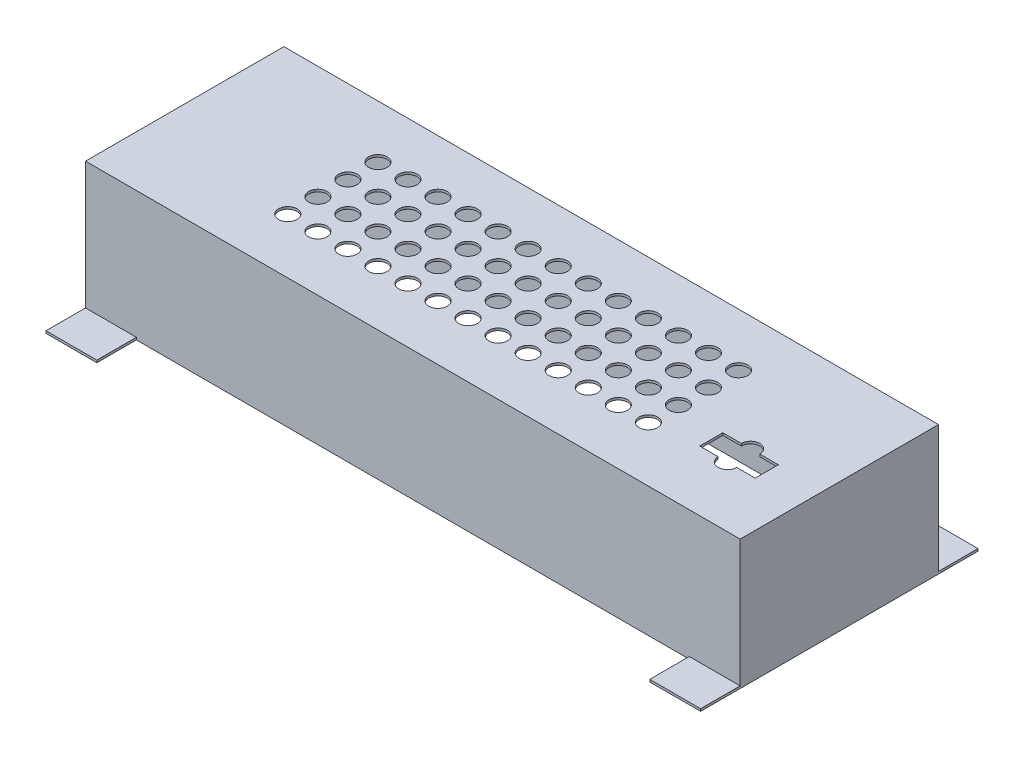
SolidWorks part; units mm, degrees
material "Lega 1060"
ref_plane "Piano frontale" through (0, 0, 0) normal (0, 0, 1) x (1, 0, 0)
ref_plane "Piano superiore" through (0, 0, 0) normal (0, 1, 0) x (1, 0, 0)
ref_plane "Piano destro" through (0, 0, 0) normal (1, 0, 0) x (0, 0, -1)
sketch "Schizzo1" plane through (0, 0, 0) normal (0, 1, 0) x (1, 0, 0)
  line L1 (-70.8, -21.45) -> (70.8, -21.45)
  line L2 (-70.8, -21.45) -> (-70.8, 21.45)
  line L3 (-70.8, 21.45) -> (70.8, 21.45)
  line L4 (70.8, -21.45) -> (70.8, 21.45)
  line L5 (-70.8, -21.45) -> (70.8, 21.45) construction
  line L6 (-70.8, 21.45) -> (70.8, -21.45) construction
  point P0 (0, 0)
  dimension "D1" = 141.6
  dimension "D2" = 42.9
extrude "Estrusione-Estrusione1" add sketch "Schizzo1" along normal blind 28
shell "Svuota1" thickness 0.5 removed face at (0, 0, 0)
hole_wizard "Foro Ø4.0 (4)-1" positions "Schizzo3" profile "Schizzo2" hole size "Ø4.0" standard "Ansi Metric"
sketch "Schizzo3" plane through (0, 28, 0) normal (0, 1, 0) x (1, 0, 0)
  line L0 (-39, 10) -> (0, 10) construction
  line L1 (0, 10) -> (0, 0) construction
  point P0 (-39, 10)
  dimension "D1" = 39
  dimension "D2" = 10
sketch "Schizzo2" plane through (-39, 28, -10) normal (1, 0, 0) x (0, 0, 1)
  line L0 (0, 0) -> (0, 7.2017)
  line L1 (0, 7.2017) -> (2, 6)
  line L2 (2, 6) -> (2, 0)
  line L5 (2, 0) -> (0, 0)
  line L10 (0, 7.2017) -> (-2, 6) construction
  line L11 (0, -6.35) -> (0, 107.95) construction
  dimension "Hole Dia." = 4
  dimension "Hole Depth" = 6
  dimension "Drill Angle" = 118
pattern_linear "Ripetizione a L1" count 13 spacing 6.5 along (1, 0, 0) count 4 spacing 6.5 along (0, 0, 1) of "Foro Ø4.0 (4)-1"
sketch "Schizzo4" plane through (0, 28, 0) normal (0, 1, 0) x (1, 0, 0)
  line L0 (0, 0) -> (55, 0) construction
  line L1 (49, -8.4) -> (61, -8.4)
  line L2 (49, -8.4) -> (49, -3.4)
  line L3 (49, -3.4) -> (61, -3.4)
  line L4 (61, -8.4) -> (61, -3.4)
  line L5 (49, -8.4) -> (61, -3.4) construction
  line L6 (49, -3.4) -> (61, -8.4) construction
  line L7 (55, 0) -> (55, -5.9) construction
  point P0 (55, -5.9)
  dimension "D1" = 12
  dimension "D2" = 5
  dimension "D3" = 5.9
  dimension "D4" = 55
extrude "Taglio-Estrusione1" cut sketch "Schizzo4" against normal blind 28
sketch "Schizzo6" plane through (0, 28, 0) normal (0, 1, 0) x (1, 0, 0)
  line L0 (61, -3.4) -> (49, -3.4) construction
  line L2 (49, -8.4) -> (61, -8.4) construction
  line L3 (53, -3.4) -> (57, -3.4)
  line L4 (57, -8.4) -> (53, -8.4)
  arc A0 (57, -3.4) -> (53, -3.4) centre (55, -3.4) ccw
  arc A1 (53, -8.4) -> (57, -8.4) centre (55, -8.4) ccw
  dimension "D1" = 2
extrude "Taglio-Estrusione2" cut sketch "Schizzo6" against normal blind 28
sketch "Schizzo8" plane through (0, 0, 0) normal (0, 1, 0) x (1, 0, 0)
  line L1 (-70.8, 21.45) -> (-59.8, 21.45)
  line L2 (-70.8, 21.45) -> (-70.8, 30)
  line L3 (-70.8, 30) -> (-59.8, 30)
  line L4 (-59.8, 21.45) -> (-59.8, 30)
  line L5 (-70.8, -21.45) -> (-59.8, -21.45)
  line L6 (-70.8, -21.45) -> (-70.8, -30)
  line L7 (-70.8, -30) -> (-59.8, -30)
  line L8 (-59.8, -21.45) -> (-59.8, -30)
  dimension "D1" = 60
  dimension "D2" = 11
extrude "Estrusione-Estrusione2" add sketch "Schizzo8" along normal blind 0.5
pattern_linear "Ripetizione a L2" count 2 spacing 130.6 along (1, 0, 0) of "Estrusione-Estrusione2"
